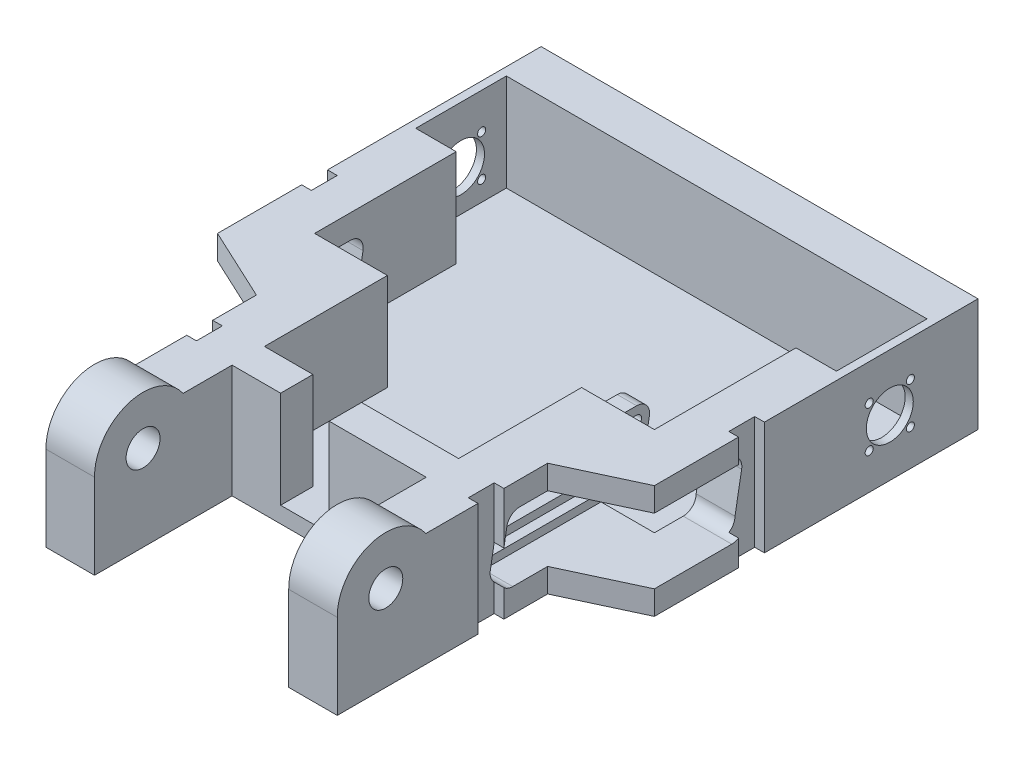
SolidWorks part; units mm, degrees
material "Custom Plastic"
ref_plane "Front Plane" through (0, 0, 0) normal (0, 0, 1) x (1, 0, 0)
ref_plane "Top Plane" through (0, 0, 0) normal (0, 1, 0) x (1, 0, 0)
ref_plane "Right Plane" through (0, 0, 0) normal (1, 0, 0) x (0, 0, -1)
sketch "Sketch1" plane through (0, 0, 0) normal (0, 1, 0) x (1, 0, 0)
  line L0 (30, 0) -> (52.5, 0)
  line L1 (0, 0) -> (0, 85) construction
  line L2 (-52.5, 0) -> (52.5, 0) construction
  line L4 (-30, 0) -> (-30, -38)
  line L6 (30, 0) -> (30, -38)
  line L7 (0, 0) -> (0, -75.5) construction
  line L8 (-30, 0) -> (0, 0) construction
  line L9 (-30, -48) -> (30, -48)
  line L10 (0, 0) -> (30, 0) construction
  line L13 (-30, -38) -> (30, -38)
  line L14 (-67.5, -15) -> (-67.5, 85)
  line L15 (-52.5, 0) -> (-30, 0)
  line L16 (-52.5, 0) -> (-52.5, 70)
  line L17 (-52.5, 70) -> (52.5, 70)
  line L18 (52.5, 0) -> (52.5, 70)
  line L19 (-67.5, 85) -> (67.5, 85)
  line L20 (67.5, -15) -> (67.5, 85)
  line L22 (-45, -25.4919) -> (-45, -75.5)
  line L26 (-30, -75.5) -> (-45, -75.5)
  line L27 (30, -75.5) -> (45, -75.5)
  line L29 (-45, 15) -> (-45, -90.5) construction
  line L30 (-45, -90.5) -> (45, -90.5) construction
  line L31 (45, 15) -> (45, -90.5) construction
  line L32 (-67.5, -15) -> (67.5, -15) construction
  line L33 (45, -25.4919) -> (45, -75.5)
  line L34 (-30, -48) -> (-30, -75.5)
  line L35 (30, -48) -> (30, -75.5)
  line L36 (-30, 0) -> (-30, -75.5) construction
  line L37 (-67.5, -15) -> (-45, -25.4919)
  line L38 (30, 0) -> (30, -75.5) construction
  line L39 (-30, -75.5) -> (30, -75.5) construction
  line L40 (67.5, -15) -> (45, -25.4919)
  line L41 (-45, 15) -> (45, 15) construction
  line L42 (-30, 0) -> (30, 0) construction
  point P0 (0, 70)
  dimension "D1" = 60
  dimension "D2" = 27.5
  dimension "D3" = 38
  dimension "D5" = 10
  dimension "D10" = 65
  dimension "D12" = 105
  dimension "D14" = 70
  dimension "D16" = 65
  dimension "D15" = 15
extrude "Boss-Extrude1" add sketch "Sketch1" along normal blind 30 contours L40 L20 L19 L14 L37 L22 L26 L34 L9 L35 L27 L33 L18 L15 L6 L13 L4 L16 L17 region at (-32.0973, 0, 61.75)
sketch "Sketch2" plane through (0, 0, 0) normal (0, -1, 0) x (1, 0, 0)
  line L0 (-45, 75.5) -> (-45, 25.4919)
  line L1 (-45, 25.4919) -> (-45, 75.5) construction
  line L2 (-45, 25.4919) -> (-67.5, 15)
  line L3 (-67.5, 15) -> (-67.5, -85)
  line L4 (-67.5, -85) -> (67.5, -85)
  line L5 (67.5, -85) -> (67.5, 15)
  line L6 (67.5, 15) -> (45, 25.4919)
  line L7 (45, 25.4919) -> (45, 75.5)
  line L8 (45, 75.5) -> (30, 75.5)
  line L9 (30, 75.5) -> (30, 48)
  line L10 (30, 48) -> (-30, 48)
  line L11 (-30, 48) -> (-30, 75.5)
  line L12 (-30, 75.5) -> (-45, 75.5)
extrude "Boss-Extrude2" add sketch "Sketch2" along normal blind 5
sketch "Sketch3" plane through (-45, 0, 0) normal (-1, 0, 0) x (0, 0, 1)
  line L0 (75.5, 30) -> (75.5, -5)
  line L1 (75.5, -5) -> (135.5, -5) construction
  line L2 (135.5, -5) -> (90.4979, 21.2512) construction
  line L3 (135.5, -5) -> (135.5, 48) construction
  line L4 (135.5, 21.5) -> (75.5, 21.5) construction
  line L5 (75.5, 30) -> (63.1408, 30)
  line L6 (25.4919, 30) -> (75.5, 30) construction
  line L7 (90.4979, 21.2512) -> (90.4979, -5)
  line L8 (75.5, -5) -> (90.4979, -5)
  circle A0 centre (75.5, 21.5) radius 5
  arc A1 (90.4979, 21.2512) -> (63.1408, 30) centre (75.5, 21.5) ccw
  line M9 (75.5, -5) -> (75.5, 30)
  line M10 (75.5, 30) -> (25.4919, 30)
  dimension "D3" = 10
  dimension "D4" = 10
  dimension "D1" = 60
  dimension "D2" = 53
  dimension "D5" = 14.9979
extrude "Boss-Extrude3" add sketch "Sketch3" against normal blind 15 contours L2 A1 A0 L1 M10 M9 region at (-45, 15.5608, 81.8436)
extrude "Boss-Extrude6" add sketch "Sketch3<3>" along normal up to surface (-75 mm away) from surface contours L7 A1 A0 L8 M10 M9 region at (-45, 15.5608, 81.8436) up to face at (30, 12.5, 61.75) starting at face at (45, 12.5, 50.496)
sketch "Sketch3<3>" plane through (-45, 0, 0) normal (-1, 0, 0) x (0, 0, 1) same geometry as "Sketch3"
sketch "Sketch5" plane through (45, 0, 0) normal (1, 0, 0) x (0, 0, -1)
  line L0 (-75.5, 26.5) -> (-75.5, 16.5) construction
  circle A0 centre (-75.5, 21.5) radius 5.25
  dimension "D1" = 10.5
extrude "Cut-Extrude1" cut sketch "Sketch5" against normal blind 100
sketch "Sketch6" plane through (0, 0, 48) normal (0, 0, 1) x (1, 0, 0)
  line L0 (-30, 30) -> (-30, -5) construction
  line L1 (-15, 30) -> (0, 30)
  line L2 (-15, 30) -> (-15, 0)
  line L3 (-15, 0) -> (0, 0)
  line L4 (0, 30) -> (0, 0)
  line L5 (-30, 30) -> (30, 30) construction
  dimension "D1" = 15
extrude "Cut-Extrude2" cut sketch "Sketch6" against normal blind 13
sketch "Sketch11" plane through (52.5, 0, 0) normal (-1, 0, 0) x (0, 0, 1)
  line L0 (-57.75, 30) -> (-57.75, 0) construction
  line L1 (15, 30) -> (-85, 30) construction
  line L2 (-64.114, 18.864) -> (-57.75, 12.5)
  line L3 (-57.75, 12.5) -> (-51.386, 6.136)
  line L4 (-64.114, 6.136) -> (-57.75, 12.5)
  line L5 (-57.75, 12.5) -> (-51.386, 18.864)
  line L6 (-65, 12.5) -> (-85, 12.5) construction
  line L7 (-85, 30) -> (-85, -5) construction
  circle A0 centre (-57.75, 12.5) radius 7.25
  circle A1 centre (-51.386, 18.864) radius 1.25
  circle A2 centre (-64.114, 18.864) radius 1.25
  circle A3 centre (-64.114, 6.136) radius 1.25
  circle A4 centre (-51.386, 6.136) radius 1.25
  dimension "D2" = 14.5
  dimension "D8" = 2.5
  dimension "D9" = 2.5
  dimension "D10" = 2.5
  dimension "D1" = 30
  dimension "D3" = 17.5
  dimension "D4" = 9
  dimension "D5" = 9
  dimension "D6" = 9
  dimension "D7" = 9
  dimension "D11" = 45
  dimension "D12" = 45
  dimension "D13" = 20
extrude "Cut-Extrude5" cut sketch "Sketch11" along normal through all both and the other way through all contours L3 A0 L5 | A2 | L2 A0 L4 | L5 A0 L2 | L4 A0 L3 | A3 | A4 | A1 region at (52.5, 19.9861, -51.8509) region at (52.5, 7.2582, -50.9212) region at (52.5, 6.6009, -62.9918) region at (52.5, 16.8515, -57.75) region at (52.5, 12.5, -62.1015) region at (52.5, 19.3288, -65.2361) region at (52.5, 12.5, -53.3985) region at (52.5, 8.1485, -57.75)
sketch "Sketch12" plane through (0, 0, 0) normal (1, 0, 0) x (0, 0, -1)
  line L0 (40.0628, 12.5) -> (72.6439, 12.5) construction
  line L1 (57.75, 27.3414) -> (57.75, 3.0865) construction
  line L2 (-15, 30) -> (85, 30) construction
  line L3 (43.75, 30) -> (71.75, 30)
  line L4 (43.75, 30) -> (43.75, 0)
  line L5 (43.75, 0) -> (71.75, 0)
  line L6 (71.75, 30) -> (71.75, 0)
  dimension "D1" = 28
  dimension "D2" = 14
  dimension "D3" = 30
extrude "Cut-Extrude6" cut sketch "Sketch12" against normal blind 65 and the other way blind 65
sketch "Sketch13" plane through (0, 30, 0) normal (0, 1, 0) x (1, 0, 0)
  line L0 (0, -43) -> (45, -43) construction
  line L1 (0, -38) -> (0, -48) construction
  line L2 (45, -25.4919) -> (45, -63.1408) construction
  line L3 (45, -43) -> (45, -39)
  line L4 (45, -43) -> (45, -47)
  line L5 (45, -39) -> (42, -39)
  line L6 (42, -39) -> (42, -47)
  line L7 (42, -47) -> (45, -47)
  line L8 (0, 85) -> (0, -70.9113) construction
  line L9 (-67.5, 85) -> (67.5, 85) construction
  line L10 (67.5, 85) -> (67.5, 15) construction
  line L11 (67.5, -15) -> (67.5, 85) construction
  line L12 (67.5, 15) -> (67.5, 19)
  line L13 (67.5, 15) -> (67.5, 11)
  line L14 (67.5, 19) -> (64.5, 19)
  line L15 (64.5, 19) -> (64.5, 11)
  line L16 (64.5, 11) -> (67.5, 11)
  line L17 (-64.5, 19) -> (-64.5, 11)
  line L18 (-67.5, 19) -> (-64.5, 19)
  line L19 (-67.5, 15) -> (-67.5, 19)
  line L20 (-67.5, 15) -> (-67.5, 11)
  line L21 (-64.5, 11) -> (-67.5, 11)
  line L22 (-42, -39) -> (-42, -47)
  line L23 (-45, -39) -> (-42, -39)
  line L24 (-45, -43) -> (-45, -39)
  line L25 (-45, -43) -> (-45, -47)
  line L26 (-42, -47) -> (-45, -47)
  dimension "D1" = 4
  dimension "D2" = 4
  dimension "D3" = 3
  dimension "D4" = 70
  dimension "D5" = 4
  dimension "D6" = 4
  dimension "D7" = 3
extrude "Cut-Extrude7" cut sketch "Sketch13" against normal blind 65
sketch "Sketch20" plane through (0, 0, 0) normal (1, 0, 0) x (0, 0, -1)
  line L0 (-29, 12.5) -> (3.7571, 12.5) construction
  line L1 (-29, 14.625) -> (3.7571, 14.625)
  line L2 (-29, 10.375) -> (3.7571, 10.375)
  line L3 (-34.1531, 18.6193) -> (11.0238, 18.6193) construction
  line L4 (-34.1531, 20.1193) -> (11.0238, 20.1193)
  line L5 (-34.1531, 17.1193) -> (11.0238, 17.1193)
  line L6 (-36.2667, 6.3807) -> (8.9102, 6.3807) construction
  line L7 (-36.2667, 7.8807) -> (8.9102, 7.8807)
  line L8 (-36.2667, 4.8807) -> (8.9102, 4.8807)
  line L9 (-34.1531, 18.6193) -> (-23.8469, 6.3807) construction
  line L10 (-36.2667, 6.3807) -> (-21.7333, 18.6193) construction
  line L11 (8.9102, 6.3807) -> (-1.396, 18.6193) construction
  line L12 (-3.5095, 6.3807) -> (11.0238, 18.6193) construction
  line L13 (-48, 30) -> (-48, -5) construction
  line L14 (-12.6214, 30) -> (-12.6214, -5) construction
  line L15 (-25.4919, 30) -> (-39, 30) construction
  line L17 (-47, 30) -> (-63.1408, 30) construction
  line L18 (-48, 30) -> (-48, 0) construction
  line L19 (-29, 27.5) -> (3.7571, 27.5)
  line L20 (3.7571, -2.5) -> (-29, -2.5)
  line L21 (-34.1531, 22.6193) -> (11.0238, 22.6193) construction
  line L22 (-34.1531, 14.6193) -> (11.0238, 14.6193) construction
  line L23 (-36.2667, 10.3807) -> (8.9102, 10.3807) construction
  line L24 (-36.2667, 2.3807) -> (8.9102, 2.3807) construction
  line L25 (-38.0947, 19.3) -> (-40.2083, 7.0614)
  line L26 (-36.2667, 2.3807) -> (8.9102, 2.3807)
  line L27 (12.9102, 6.3807) -> (14.962, 17.919)
  line L28 (11.0238, 22.6193) -> (-34.1531, 22.6193)
  line L31 (-39, -5) -> (-25.4919, -5) construction
  arc A0 (-29, 14.625) -> (-29, 10.375) centre (-29, 12.5) ccw
  arc A1 (3.7571, 10.375) -> (3.7571, 14.625) centre (3.7571, 12.5) ccw
  arc A2 (-34.1531, 20.1193) -> (-34.1531, 17.1193) centre (-34.1531, 18.6193) ccw
  arc A3 (11.0238, 17.1193) -> (11.0238, 20.1193) centre (11.0238, 18.6193) ccw
  arc A4 (-36.2667, 7.8807) -> (-36.2667, 4.8807) centre (-36.2667, 6.3807) ccw
  arc A5 (8.9102, 4.8807) -> (8.9102, 7.8807) centre (8.9102, 6.3807) ccw
  circle A6 centre (-29, 12.5) radius 15
  circle A7 centre (3.7571, 12.5) radius 15
  arc A8 (11.0238, 14.6193) -> (11.0238, 22.6193) centre (11.0238, 18.6193) ccw construction
  arc A9 (-34.1531, 22.6193) -> (-34.1531, 14.6193) centre (-34.1531, 18.6193) ccw construction
  arc A10 (8.9102, 2.3807) -> (8.9102, 10.3807) centre (8.9102, 6.3807) ccw construction
  arc A11 (-36.2667, 10.3807) -> (-36.2667, 2.3807) centre (-36.2667, 6.3807) ccw construction
  arc A13 (8.9102, 2.3807) -> (12.9102, 6.3807) centre (8.9102, 6.3807) ccw
  arc A14 (14.962, 17.919) -> (11.0238, 22.6193) centre (11.0238, 18.6193) ccw
  arc A15 (-34.1531, 22.6193) -> (-38.0947, 19.3) centre (-34.1531, 18.6193) ccw
  arc A16 (-40.2083, 7.0614) -> (-36.2667, 2.3807) centre (-36.2667, 6.3807) ccw
  point P2 (-12.6214, 12.5)
  point P7 (-11.5647, 18.6193)
  point P14 (-13.6782, 6.3807)
  point P24 (-29, 12.5)
  point P27 (-29, 12.5)
  point P30 (3.7571, 12.5)
  point P33 (3.7571, 12.5)
  point P42 (0, 0)
  point P43 (0, 0)
  point P67 (0, 0)
  point P73 (0, 0)
  point P77 (0, 0)
  point P78 (0, 0)
  dimension "D3" = 1.5
  dimension "D6" = 30
  dimension "D7" = 4
  dimension "D1" = 19
  dimension "D2" = 16
  dimension "D4" = 4.25
  dimension "D5" = 10.1687
  dimension "D8" = 2.5
extrude "Cut-Extrude9" cut sketch "Sketch20<3>" against normal offset from surface (31.5 mm away) 6 from surface contours L25 A16 L26 A13 L27 A14 L28 A15 up to face at (30, 15, 19) starting at face at (67.5, 6.136, -62.864)
sketch "Sketch20<3>" plane through (0, 0, 0) normal (1, 0, 0) x (0, 0, -1) same geometry as "Sketch20"
extrude "Cut-Extrude10" cut sketch "Sketch20<5>" along normal offset from surface (31.5 mm away) 6 from surface contours L27 A14 L28 A15 L25 A16 L26 A13 up to face at (-30, 15, 19) starting at face at (-67.5, 12.5, 2)
sketch "Sketch20<5>" plane through (0, 0, 0) normal (1, 0, 0) x (0, 0, -1) same geometry as "Sketch20"
extrude "Boss-Extrude7" add sketch "Sketch20<4>" against normal up to surface (-30 mm away) from surface contours L27 A14 L28 A15 L25 A16 L26 A13 up to face at (30, 15, 19) starting at face at (36, 12.694, 25.0696)
sketch "Sketch20<4>" plane through (0, 0, 0) normal (1, 0, 0) x (0, 0, -1) same geometry as "Sketch20"
extrude "Cut-Extrude8" cut sketch "Sketch20" against normal up to surface (-30 mm away) from surface contours L4 A3 L5 A2 | A4 L8 A5 L7 | A0 L2 A1 L1 up to face at (30, 13.439, 2.6268) starting at face at (67.5, -0.4826, -0.1902)
extrude "Cut-Extrude11" cut sketch "Sketch20<6>" along normal up to surface (30 mm away) from surface contours A7 L19 A6 L28 | A7 L26 A6 L20 | A7 | A6 region at (0, 25.4621, 12.6214) region at (0, -0.4621, 12.6214) up to face at (30, 6.3807, 13.6782) starting at face at (0, 15, 43)
sketch "Sketch20<6>" plane through (0, 0, 0) normal (1, 0, 0) x (0, 0, -1) same geometry as "Sketch20"
